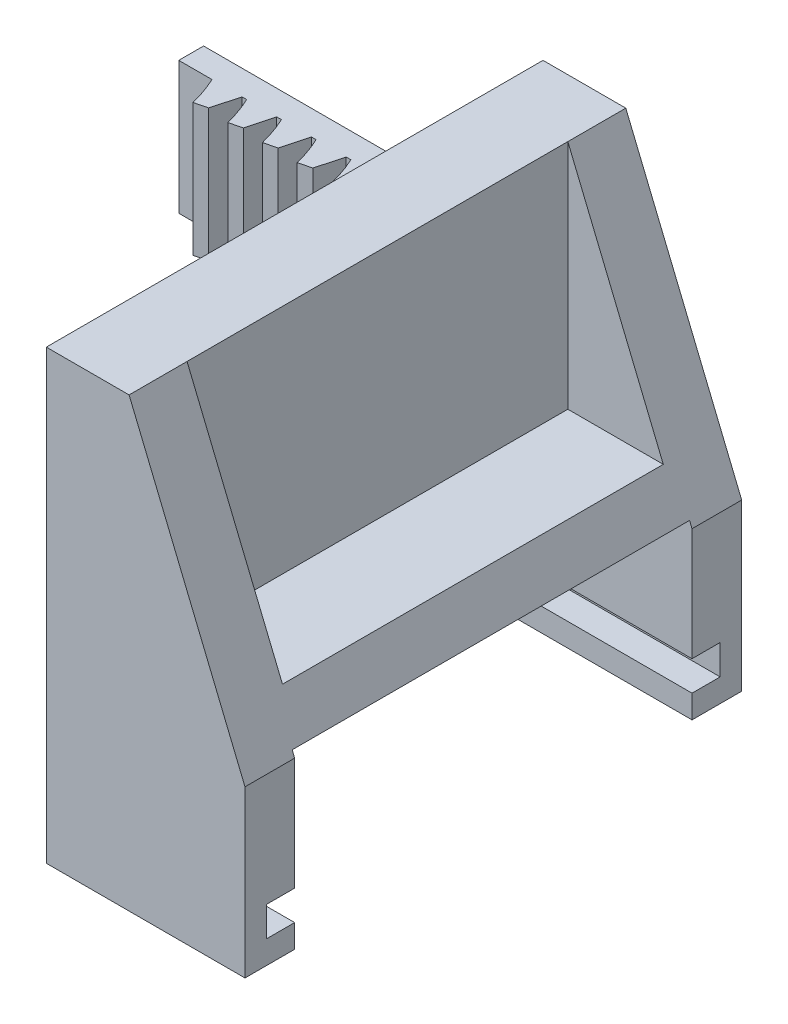
SolidWorks part; units mm, degrees
ref_plane "Front Plane" through (0, 0, 0) normal (0, 0, 1) x (1, 0, 0)
ref_plane "Top Plane" through (0, 0, 0) normal (0, 1, 0) x (1, 0, 0)
ref_plane "Right Plane" through (0, 0, 0) normal (1, 0, 0) x (0, 0, -1)
sketch "Sketch1" plane through (0, 0, 0) normal (0, 0, 1) x (1, 0, 0)
  line L0 (0, 0) -> (0, -27)
  line L1 (0, -27) -> (12, -27)
  line L2 (12, -27) -> (12, -17)
  line L3 (12, -17) -> (5, 0)
  line L4 (5, 0) -> (0, 0)
  dimension "D1" = 27
  dimension "D2" = 12
  dimension "D3" = 10
  dimension "D4" = 5
extrude "Boss-Extrude1" add sketch "Sketch1" against normal blind 30
sketch "Sketch4" plane through (0, 0, 0) normal (-1, 0, 0) x (0, 0, 1)
  line L0 (-30, 0) -> (-30, -27) construction
  line L1 (-27, -16.6386) -> (-3, -16.6386)
  line L2 (-27, -16.6386) -> (-27, -28.6386)
  line L3 (-27, -28.6386) -> (-3, -28.6386)
  line L4 (-3, -16.6386) -> (-3, -28.6386)
  point P4 (-27, -22.6386)
  dimension "D1" = 24
  dimension "D2" = 12
  dimension "D3" = 3
extrude "Cut-Extrude2" cut sketch "Sketch4" against normal blind 25 contours L2 L1 L4 L3
sketch "Sketch5" plane through (0, 0, 0) normal (-1, 0, 0) x (0, 0, 1)
  line L0 (-3, -16.6386) -> (-3, -27) construction
  line L1 (-3, -23.8) -> (-1.3, -23.8)
  line L2 (-3, -23.8) -> (-3, -25.6)
  line L3 (-3, -25.6) -> (-1.3, -25.6)
  line L4 (-1.3, -23.8) -> (-1.3, -25.6)
  line L5 (-3, -27) -> (0, -27) construction
  dimension "D1" = 1.8
  dimension "D2" = 1.7
  dimension "D3" = 1.4
extrude "Cut-Extrude3" cut sketch "Sketch5" against normal blind 15
ref_plane "Plane1" through (0, 0, -15) normal (0, 0, 1) x (1, 0, 0)
mirror "Mirror1" about plane through (0, 0, -15) normal (0, 0, 1) of "Cut-Extrude3"
sketch "Sketch6" plane through (0, 0, -15) normal (0, 0, 1) x (1, 0, 0)
  line L0 (5, 0) -> (5, -14)
  line L1 (5, -14) -> (10.7647, -14)
  line L2 (12, -17) -> (5, 0) construction
  line L3 (10.7647, -14) -> (5, 0)
  dimension "D1" = 14
extrude "Cut-Extrude4" cut sketch "Sketch6" against normal mid plane 23
ref_plane "Plane2" through (0, -16, 0) normal (0, 1, 0) x (1, 0, 0)
sketch "Sketch7" plane through (0, -16, 0) normal (0, 1, 0) x (1, 0, 0)
  line L0 (0, 28.5) -> (-19, 28.5)
  line L1 (0, 30) -> (0, 0) construction
  line L3 (0, 28.5) -> (0, 27)
  line L4 (0, 27) -> (-0.5, 27)
  line L47 (-0.5, 27) -> (-0.9304, 25.4151)
  line L62 (-6.6, 15) -> (6.6, 15) construction
  line L108 (-19, 27) -> (-19, 28.5)
  line L112 (-0.9304, 25.4151) -> (-1.6865, 25.2276)
  line L113 (-2.3144, 27) -> (-2.597, 27)
  line L114 (-3.0274, 25.4151) -> (-3.7835, 25.2276)
  line L115 (-2.597, 27) -> (-3.0274, 25.4151)
  line L116 (-5.1244, 25.4151) -> (-5.8805, 25.2276)
  line L117 (-4.694, 27) -> (-5.1244, 25.4151)
  line L118 (-7.2214, 25.4151) -> (-7.9775, 25.2276)
  line L119 (-6.791, 27) -> (-7.2214, 25.4151)
  line L120 (-9.3184, 25.4151) -> (-10.0745, 25.2276)
  line L121 (-8.888, 27) -> (-9.3184, 25.4151)
  line L122 (-11.4154, 25.4151) -> (-12.1715, 25.2276)
  line L123 (-10.985, 27) -> (-11.4154, 25.4151)
  line L124 (-13.5124, 25.4151) -> (-14.2685, 25.2276)
  line L125 (-13.082, 27) -> (-13.5124, 25.4151)
  line L126 (-4.4114, 27) -> (-4.694, 27)
  line L127 (-6.5085, 27) -> (-6.791, 27)
  line L128 (-8.6055, 27) -> (-8.888, 27)
  line L129 (-10.7025, 27) -> (-10.985, 27)
  line L130 (-12.7995, 27) -> (-13.082, 27)
  line L132 (-15.6094, 25.4151) -> (-16.3655, 25.2276)
  line L133 (-15.179, 27) -> (-15.6094, 25.4151)
  line L134 (-14.8965, 27) -> (-15.179, 27)
  line L135 (-16.9935, 27) -> (-19, 27)
  arc A0 (-1.6865, 25.2276) -> (-2.3144, 27) centre (-11.0716, 22.8998) ccw
  arc A1 (-3.7835, 25.2276) -> (-4.4114, 27) centre (-13.1686, 22.8998) ccw
  arc A2 (-5.8805, 25.2276) -> (-6.5085, 27) centre (-15.2656, 22.8998) ccw
  arc A3 (-7.9775, 25.2276) -> (-8.6055, 27) centre (-17.3626, 22.8998) ccw
  arc A4 (-10.0745, 25.2276) -> (-10.7025, 27) centre (-19.4596, 22.8998) ccw
  arc A5 (-12.1715, 25.2276) -> (-12.7995, 27) centre (-21.5566, 22.8998) ccw
  arc A6 (-14.2685, 25.2276) -> (-14.8965, 27) centre (-23.6536, 22.8998) ccw
  arc A7 (-16.3655, 25.2276) -> (-16.9935, 27) centre (-25.7506, 22.8998) ccw
  point P10 (-3.7638, 25.1467)
  point P47 (-0.9304, 25.4151)
  dimension "D1" = 7
  dimension "D4" = 8
  dimension "D2" = 19
  dimension "D3" = 1.5
  dimension "D6" = 0.5
  dimension "D7" = 13.5
extrude "Boss-Extrude2" add sketch "Sketch7" along normal blind 8
